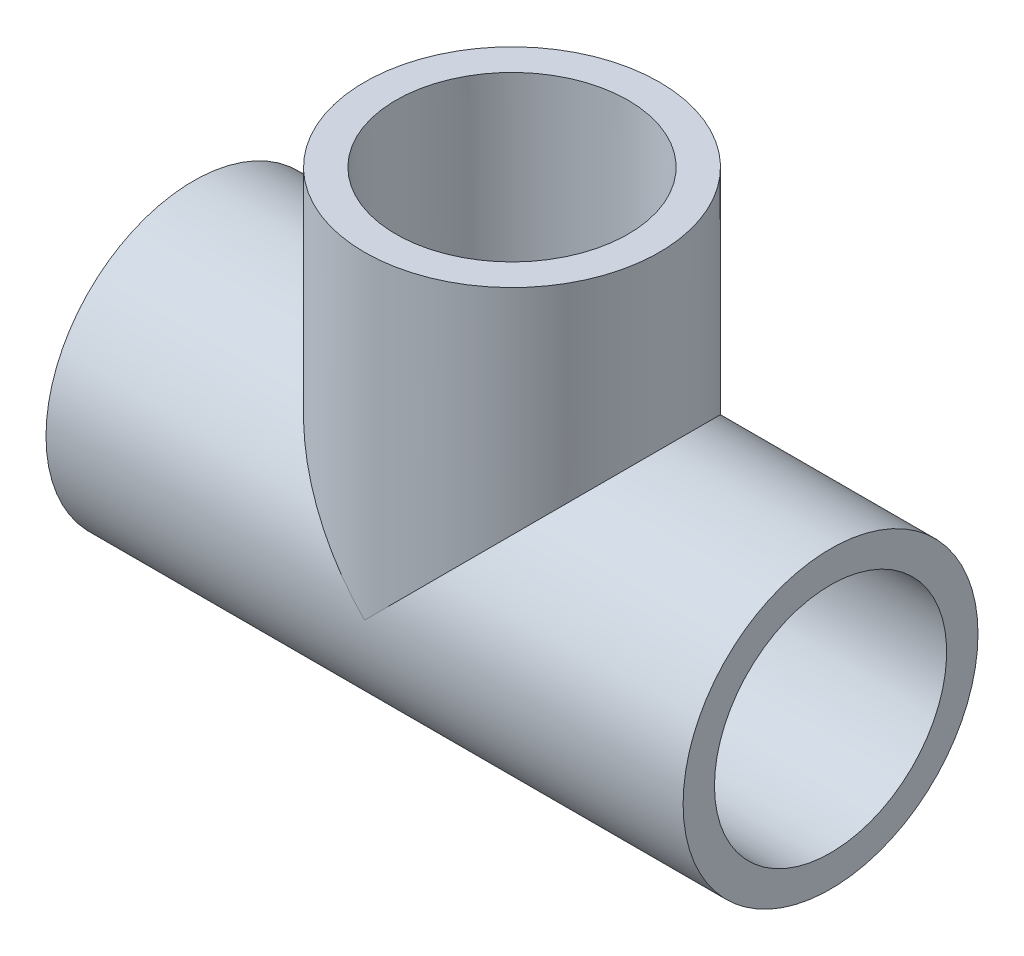
SolidWorks part; units mm, degrees
ref_plane "Front Plane" through (0, 0, 0) normal (0, 0, 1) x (1, 0, 0)
ref_plane "Top Plane" through (0, 0, 0) normal (0, 1, 0) x (1, 0, 0)
ref_plane "Right Plane" through (0, 0, 0) normal (1, 0, 0) x (0, 0, -1)
sketch "Sketch0" plane through (0, 0, 0) normal (0, 0, 1) x (1, 0, 0)
  line L0 (-46.1772, 0) -> (0, 0) construction
  line L1 (0, 0) -> (0, 46.1772) construction
  line L2 (-17.4752, 0) -> (0, 0) construction
  line L3 (0, 0) -> (0, 17.4752) construction
  line L4 (-46.1772, 21.3741) -> (-46.1772, -21.3741) construction
  line L5 (-17.4752, 16.637) -> (-46.1772, 16.8275) construction
  line L6 (-17.4752, 16.637) -> (-17.4752, -16.637) construction
  line L7 (-17.4752, -16.637) -> (-46.1772, -16.8275) construction
  line L8 (-46.1772, 16.8275) -> (-46.1772, -16.8275) construction
  line L9 (-21.3741, 46.1772) -> (21.3741, 46.1772) construction
  line L10 (-16.8275, 46.1772) -> (16.8275, 46.1772) construction
  line L11 (16.8275, 46.1772) -> (16.637, 17.4752) construction
  line L12 (16.637, 17.4752) -> (-16.637, 17.4752) construction
  line L13 (-16.637, 17.4752) -> (-16.8275, 46.1772) construction
  line L14 (-17.4752, 12.1539) -> (-17.4752, -12.1539) construction
  line L18 (-12.1539, 17.4752) -> (12.1539, 17.4752) construction
  dimension "H" = 46.1772
  dimension "G" = 17.4752
  dimension "M" = 42.7482
  dimension "OD A" = 33.655
  dimension "OD B" = 33.274
  dimension "ID" = 24.3078
sketch "Sketch1" plane through (0, 0, 0) normal (0, 0, 1) x (1, 0, 0)
  line L0 (-46.1772, 0) -> (0, 0) construction
  line L1 (-46.1772, 0) -> (0, 0) construction
  line L3 (-46.1772, -21.3741) -> (-17.4752, -21.3741)
  line L4 (-46.1772, -21.3741) -> (-46.1772, -16.8275)
  line L5 (-46.1772, -16.8275) -> (-17.4752, -16.637)
  line L6 (-17.4752, -21.3741) -> (-17.4752, -16.637)
revolve "Revolve1" add sketch "Sketch1" angle 360 about L1
mirror "Mirror1" about plane through (0, 0, 0) normal (1, 0, 0) of bodies 102
sketch "Sketch2" plane through (0, 0, 0) normal (0, 0, 1) x (1, 0, 0)
  line L0 (16.8275, 46.1772) -> (16.637, 17.4752)
  line L1 (16.637, 17.4752) -> (21.3741, 17.4752)
  line L2 (21.3741, 17.4752) -> (21.3741, 46.1772)
  line L3 (21.3741, 46.1772) -> (16.8275, 46.1772)
  line L4 (0, 0) -> (0, 46.1772) construction
  line L5 (0, 0) -> (0, 46.1772) construction
revolve "Revolve2" add sketch "Sketch2" angle 360 about L5
sketch "Sketch3" plane through (-17.4752, 0, 0) normal (1, 0, 0) x (0, 0, -1)
  line L0 (-21.3741, 17.4752) -> (21.3741, 17.4752) construction
  line L2 (12.3073, 17.4752) -> (-12.3073, 17.4752)
  circle A1 centre (0, 0) radius 21.3741 construction
  arc A3 (-12.3073, 17.4752) -> (12.3073, 17.4752) centre (0, 0) ccw
extrude "Boss-Extrude1" add sketch "Sketch3" along normal up to surface (34.9504 mm away) up to face at (17.4752, 0, 16.637)
sketch "Sketch4" plane through (0, 17.4752, 0) normal (0, -1, 0) x (1, 0, 0)
  line L0 (17.4752, -12.3073) -> (17.4752, 12.3073)
  line L1 (-17.4752, -12.3073) -> (-17.4752, 12.3073)
  circle A0 centre (0, 0) radius 21.3741 construction
  arc A1 (17.4752, 12.3073) -> (-17.4752, 12.3073) centre (0, 0) ccw
  arc A2 (-17.4752, -12.3073) -> (17.4752, -12.3073) centre (0, 0) ccw
  circle A3 centre (0, 0) radius 21.3741 construction
  circle A4 centre (0, 0) radius 21.3741 construction
extrude "Boss-Extrude2" add sketch "Sketch4" along normal up to surface (17.4752 mm away) up to plane "Top Plane"
sketch "Sketch5" plane through (-17.4752, 0, 0) normal (-1, 0, 0) x (0, 0, 1)
  line L0 (0, 16.637) -> (0, -16.637) construction
  circle A0 centre (0, 0) radius 12.1539
extrude "Cut-Extrude1" cut sketch "Sketch5" against normal up to surface (34.9504 mm away) up to face at (17.4752, 0, 16.637)
sketch "Sketch6" plane through (0, 17.4752, 0) normal (0, 1, 0) x (1, 0, 0)
  circle A0 centre (0, 0) radius 12.1539
extrude "Cut-Extrude2" cut sketch "Sketch6" against normal up to vertex (17.4752 mm away) up to point (0, 0, 0)
other "CPoint1" parameters "Diameter"=25.4, "StubLength"=19.05
ref_axis "Axis1" through (-27.4752, 0, 0) along (1, 0, 0)
other "CPoint2" parameters "Diameter"=25.4, "StubLength"=19.05
ref_axis "Axis2" through (27.4752, 0, 0) along (-1, 0, 0)
other "CPoint3" parameters "Diameter"=25.4, "StubLength"=19.05
ref_axis "Axis3" through (0, 27.4752, 0) along (0, -1, 0)
other "RPoint1"
